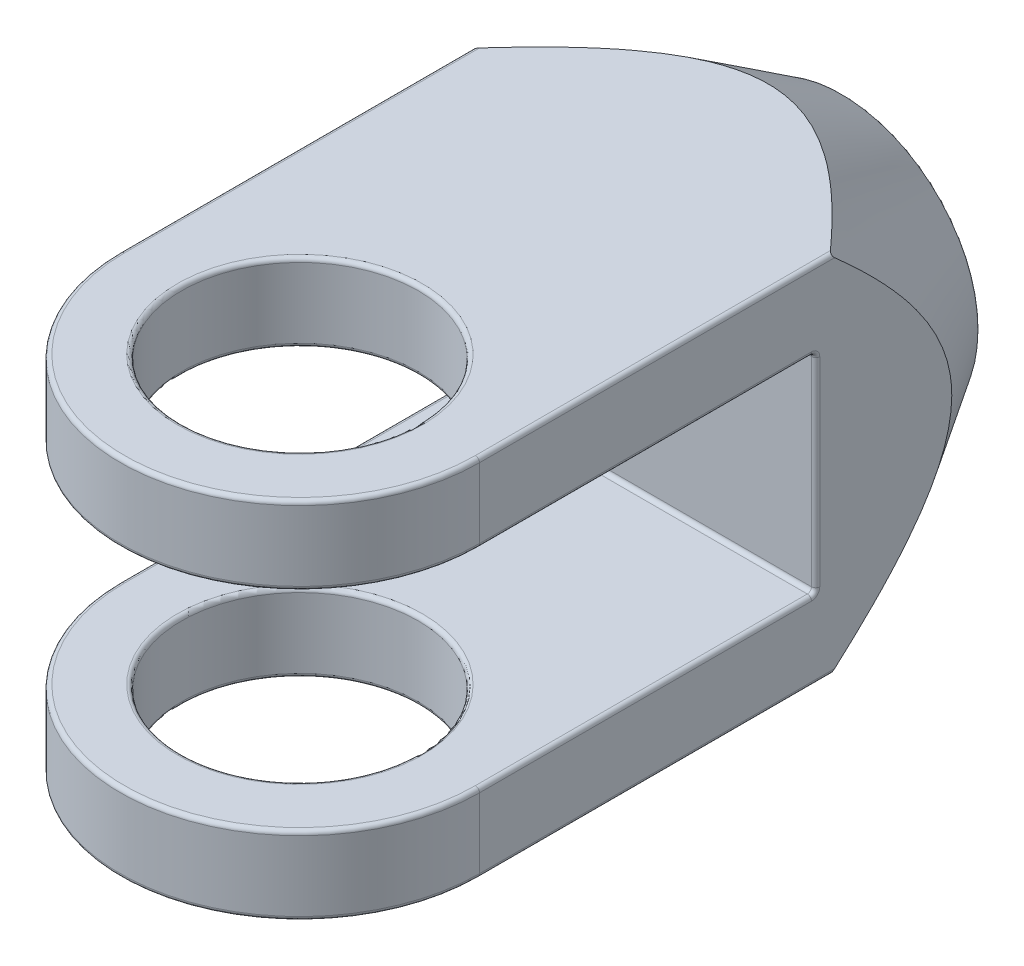
SolidWorks part; units mm, degrees
ref_plane "Front Plane" through (0, 0, 0) normal (0, 0, 1) x (1, 0, 0)
ref_plane "Top Plane" through (0, 0, 0) normal (0, 1, 0) x (1, 0, 0)
ref_plane "Right Plane" through (0, 0, 0) normal (1, 0, 0) x (0, 0, -1)
sketch "Sketch1" plane through (0, 0, 0) normal (0, 1, 0) x (1, 0, 0)
  line L0 (-997.2213, -10.9855) -> (49002.7787, -10.9855) construction
  line L2 (-10.9855, 0) -> (-10.9855, 33.2613)
  line L3 (-10.9855, 33.2613) -> (10.9855, 33.2613)
  line L4 (10.9855, 0) -> (10.9855, 33.2613)
  circle A0 centre (0, 0) radius 7.239
  arc A1 (-10.9855, 0) -> (10.9855, 0) centre (0, 0) ccw
  dimension "D1" = 14.478
  dimension "D2" = 21.971
  dimension "D3" = 44.2468
extrude "Boss-Extrude1" add sketch "Sketch1" along normal blind 22.2758
sketch "Sketch2" plane through (0, 0, 0) normal (1, 0, 0) x (0, 0, -1)
  line L0 (-10.9855, 22.2758) -> (-10.9855, 0) construction
  line L1 (-10.9855, 17.4879) -> (20.5613, 17.4879)
  line L2 (-10.9855, 17.4879) -> (-10.9855, 4.7879)
  line L3 (-10.9855, 4.7879) -> (20.5613, 4.7879)
  line L4 (20.5613, 17.4879) -> (20.5613, 4.7879)
  line L5 (33.2613, 11.1379) -> (-10.9855, 11.1379) construction
  line L6 (33.2613, 22.2758) -> (33.2613, 0) construction
  dimension "D1" = 12.7
  dimension "D2" = 6.35
  dimension "D3" = 12.7
extrude "Cut-Extrude1" cut sketch "Sketch2" against normal mid plane 25.4
sketch "Sketch3" plane through (0, 0, -33.2613) normal (0, 0, -1) x (-1, 0, 0)
  line L0 (-10.9855, 22.2758) -> (10.9855, 0) construction
  line L1 (10.9855, 22.2758) -> (-10.9855, 0) construction
  circle A0 centre (0, 11.1379) radius 8.255 construction
  dimension "D1" = 16.51
ref_plane "Plane1" through (5.5684, 5.4922, 0) normal (-0.712, -0.7022, 0) x (0, 0, 1)
sketch "Sketch5" plane through (5.5684, 5.4922, 0) normal (-0.712, -0.7022, 0) x (0, 0, 1)
  line L0 (-21.4365, 23.5737) -> (-33.2613, 16.1847)
  line L1 (-33.2613, 23.5737) -> (0, 23.5737) construction
  line L2 (-33.2613, 16.1847) -> (-33.2613, -0.3253) construction
  line L3 (-33.2613, 16.1847) -> (-33.2613, 23.5737)
  line L4 (-33.2613, 23.5737) -> (-21.4365, 23.5737)
  dimension "D1" = 32
sketch "Sketch6" plane through (5.5684, 5.4922, 0) normal (-0.712, -0.7022, 0) x (0, 0, 1)
  line L0 (-33.2613, 7.9297) -> (11.4185, 7.9297) construction
revolve "Cut-Revolve1" cut sketch "Sketch5" angle 360 about L0
fillet "Fillet1" radius 0.254 2 edges at (0, 4.7879, -20.5613) (0, 17.4879, -20.5613)
fillet "Fillet2" radius 0.254 12 edges at (10.9855, 17.4135, -20.4869) (-10.9855, 17.4135, -20.4869) (-10.9855, 4.8623, -20.4869) (10.9855, 4.8623, -20.4869) (-10.9855, 11.1379, -20.5613) (-10.9855, 4.7879, -10.1536) (-10.9855, 17.4879, -10.1536) (0, 17.4879, 10.9855) (0, 4.7879, 10.9855) (10.9855, 4.7879, -10.1536) (10.9855, 17.4879, -10.1536) (10.9855, 11.1379, -20.5613)
fillet "Fillet3" radius 0.254 6 edges at (-10.9855, 22.2758, -10.7182) (0, 22.2758, 10.9855) (10.9855, 22.2758, -10.7182) (-10.9855, 0, -10.7182) (0, 0, 10.9855) (10.9855, 0, -10.7182)
fillet "Fillet4" radius 0.254 4 edges at (0, 22.2758, 7.239) (0, 17.4879, 7.239) (0, 4.7879, -7.239) (0, 0, 7.239)
fillet "Fillet5" radius 0.254 1 edges at (-8.255, 11.1379, -33.2613)
hole_wizard "1/4-20 Tapped Hole1" positions "Sketch7" profile "Sketch8" tap size "1/4-20" standard "ANSI Inch"
sketch "Sketch7" plane through (0, 0, -33.2613) normal (0, 0, -1) x (-1, 0, 0)
  line L0 (10.9855, 0.254) -> (10.9855, 22.0218) construction
  line L1 (-10.7315, 0) -> (10.7315, 0) construction
  point P0 (-0.1905, 11.176)
  dimension "D1" = 11.176
  dimension "D2" = 11.176
cosmetic thread "Hole Thread1" parameters "D2"=6.35
sketch "Sketch8" plane through (0.1905, 11.176, -33.2613) normal (1, 0, 0) x (0, 1, 0)
  line L0 (0, 0) -> (0, 18.0438)
  line L1 (0, 18.0438) -> (2.5527, 16.51)
  line L2 (2.5527, 16.51) -> (2.5527, 0)
  line L5 (2.5527, 0) -> (0, 0)
  line L10 (0, 18.0438) -> (-2.5527, 16.51) construction
  line L11 (0, -6.35) -> (0, 107.95) construction
  dimension "Tap Drill Dia." = 5.1054
  dimension "Tap Drill Depth" = 16.51
  dimension "Drill Angle" = 118
